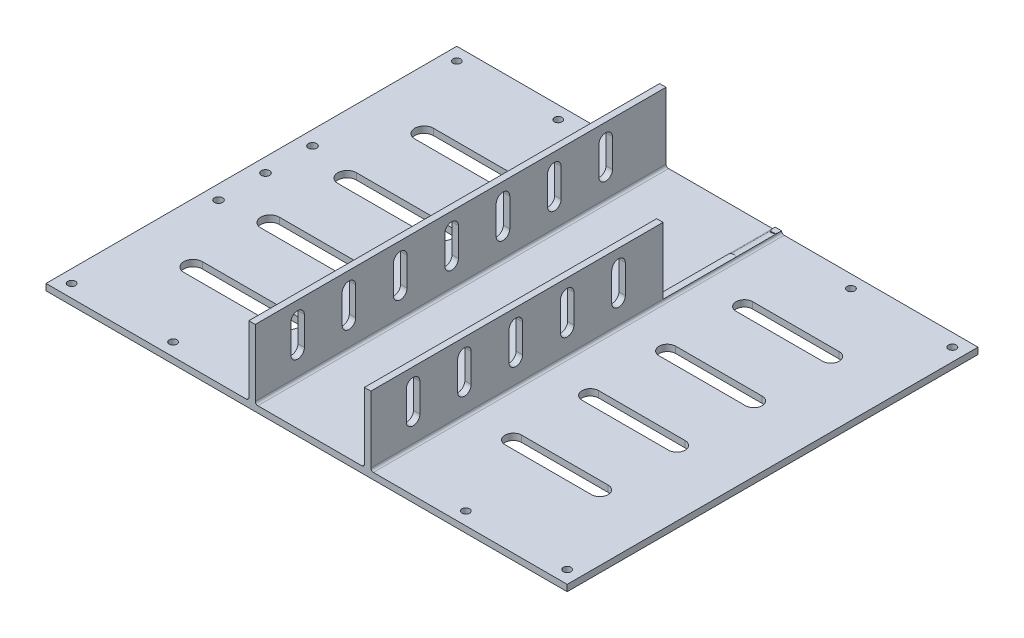
SolidWorks part; units mm, degrees
ref_plane "前视基准面" through (0, 0, 0) normal (0, 0, 1) x (1, 0, 0)
ref_plane "上视基准面" through (0, 0, 0) normal (0, 1, 0) x (1, 0, 0)
ref_plane "右视基准面" through (0, 0, 0) normal (1, 0, 0) x (0, 0, -1)
other "Configuration Table"
sketch "草图1" plane through (0, 0, 0) normal (0, 0, 1) x (1, 0, 0)
  line L0 (0, 0) -> (203, 0)
  line L1 (0, 0) -> (0, 2.5)
  line L2 (0, 2.5) -> (79, 2.5)
  line L3 (79, 2.5) -> (79, 32.5)
  line L4 (79, 32.5) -> (81.5, 32.5)
  line L5 (81.5, 32.5) -> (81.5, 2.5)
  line L6 (81.5, 2.5) -> (124, 2.5)
  line L7 (126.5, 2.5) -> (126.5, 32.5)
  line L8 (126.5, 32.5) -> (124, 32.5)
  line L9 (124, 32.5) -> (124, 2.5)
  line L11 (203, 2.5) -> (203, 0)
  line L12 (126.5, 2.5) -> (203, 2.5)
  dimension "D1" = 203
  dimension "D2" = 79
  dimension "D3" = 79
  dimension "D4" = 42.5
  dimension "D5" = 2.5
  dimension "D6" = 2.5
  dimension "D7" = 2.5
  dimension "D8" = 30
  dimension "D9" = 30
  dimension "D10" = 2.5
extrude "凸台-拉伸2" add sketch "草图1" along normal blind 160
fillet "圆角1" radius 1 1 edges at (81.5, 2.5, 80)
fillet "圆角2" radius 1 1 edges at (124, 2.5, 80)
fillet "圆角3" radius 1 2 edges at (79, 2.5, 80) (126.5, 2.5, 80)
sketch "草图2" plane through (0, 2.5, 0) normal (0, 1, 0) x (1, 0, 0)
  line L0 (78, 0) -> (0, 0) construction
  line L1 (0, -160) -> (0, 0) construction
  line L2 (78, -160) -> (0, -160) construction
  line L3 (203, -160) -> (203, 0) construction
  line L4 (203, 0) -> (127.5, 0) construction
  line L6 (203, -160) -> (127.5, -160) construction
  circle A0 centre (5, -5) radius 1.5
  circle A1 centre (5, -155) radius 1.5
  circle A2 centre (198, -5) radius 1.5
  circle A3 centre (198, -155) radius 1.5
  dimension "D9" = 3
  dimension "D10" = 3
  dimension "D11" = 3
  dimension "D12" = 3
  dimension "D1" = 5
  dimension "D2" = 5
  dimension "D3" = 5
  dimension "D4" = 5
  dimension "D5" = 5
  dimension "D6" = 5
  dimension "D7" = 5
  dimension "D8" = 5
extrude "切除-拉伸1" cut sketch "草图2" against normal blind 160
sketch "草图3" plane through (0, 2.5, 0) normal (0, 1, 0) x (1, 0, 0)
  line L0 (0, -160) -> (0, 0) construction
  line L1 (203, -160) -> (203, 0) construction
  line L4 (203, 0) -> (127.5, 0) construction
  line L5 (78, 0) -> (0, 0) construction
  line L6 (78, -160) -> (0, -160) construction
  circle A0 centre (44.5, -5) radius 1.5
  circle A1 centre (44.5, -155) radius 1.5
  circle A2 centre (158.5, -5) radius 1.5
  circle A3 centre (158.5, -155) radius 1.5
  dimension "D1" = 3
  dimension "D2" = 3
  dimension "D3" = 3
  dimension "D4" = 3
  dimension "D5" = 44.5
  dimension "D6" = 44.5
  dimension "D7" = 44.5
  dimension "D8" = 44.5
  dimension "D9" = 5
  dimension "D10" = 5
  dimension "D11" = 5
extrude "切除-拉伸2" cut sketch "草图3" against normal blind 160
sketch "草图4" plane through (0, 2.5, 0) normal (0, 1, 0) x (1, 0, 0)
  line L0 (23.0924, -35.8152) -> (60.3028, -35.8152) construction
  line L3 (23.0924, -32.1909) -> (60.3028, -32.1909)
  line L4 (23.0924, -39.4396) -> (60.3028, -39.4396)
  line L5 (23.0924, -69.4396) -> (60.3028, -69.4396)
  line L6 (23.0924, -62.1909) -> (60.3028, -62.1909)
  line L7 (23.0924, -65.8152) -> (60.3028, -65.8152) construction
  line L8 (23.0924, -99.4396) -> (60.3028, -99.4396)
  line L9 (23.0924, -92.1909) -> (60.3028, -92.1909)
  line L10 (23.0924, -95.8152) -> (60.3028, -95.8152) construction
  line L11 (23.0924, -129.4396) -> (60.3028, -129.4396)
  line L12 (23.0924, -122.1909) -> (60.3028, -122.1909)
  line L13 (23.0924, -125.8152) -> (60.3028, -125.8152) construction
  arc A2 (23.0924, -32.1909) -> (23.0924, -39.4396) centre (23.0924, -35.8152) ccw
  arc A3 (60.3028, -39.4396) -> (60.3028, -32.1909) centre (60.3028, -35.8152) ccw
  arc A4 (23.0924, -62.1909) -> (23.0924, -69.4396) centre (23.0924, -65.8152) ccw
  arc A5 (60.3028, -69.4396) -> (60.3028, -62.1909) centre (60.3028, -65.8152) ccw
  arc A6 (23.0924, -92.1909) -> (23.0924, -99.4396) centre (23.0924, -95.8152) ccw
  arc A7 (60.3028, -99.4396) -> (60.3028, -92.1909) centre (60.3028, -95.8152) ccw
  arc A8 (23.0924, -122.1909) -> (23.0924, -129.4396) centre (23.0924, -125.8152) ccw
  arc A9 (60.3028, -129.4396) -> (60.3028, -122.1909) centre (60.3028, -125.8152) ccw
  point P2 (41.6976, -35.8152)
  point P11 (41.6976, -65.8152)
  point P18 (41.6976, -95.8152)
  point P25 (41.6976, -125.8152)
  dimension "D1" = 4
extrude "切除-拉伸3" cut sketch "草图4" against normal blind 160
sketch "草图5" plane through (0, 2.5, 0) normal (0, 1, 0) x (1, 0, 0)
  line L0 (143.7888, -31.7728) -> (177.4701, -31.7728) construction
  line L1 (143.7888, -28.5294) -> (177.4701, -28.5294)
  line L2 (143.7888, -35.0162) -> (177.4701, -35.0162)
  line L3 (143.7888, -61.7728) -> (177.4701, -61.7728) construction
  line L4 (143.7888, -58.5294) -> (177.4701, -58.5294)
  line L5 (143.7888, -65.0162) -> (177.4701, -65.0162)
  line L6 (143.7888, -91.7728) -> (177.4701, -91.7728) construction
  line L7 (143.7888, -88.5294) -> (177.4701, -88.5294)
  line L8 (143.7888, -95.0162) -> (177.4701, -95.0162)
  line L9 (143.7888, -121.7728) -> (177.4701, -121.7728) construction
  line L10 (143.7888, -118.5294) -> (177.4701, -118.5294)
  line L11 (143.7888, -125.0162) -> (177.4701, -125.0162)
  arc A0 (143.7888, -28.5294) -> (143.7888, -35.0162) centre (143.7888, -31.7728) ccw
  arc A1 (177.4701, -35.0162) -> (177.4701, -28.5294) centre (177.4701, -31.7728) ccw
  arc A2 (143.7888, -58.5294) -> (143.7888, -65.0162) centre (143.7888, -61.7728) ccw
  arc A3 (177.4701, -65.0162) -> (177.4701, -58.5294) centre (177.4701, -61.7728) ccw
  arc A4 (143.7888, -88.5294) -> (143.7888, -95.0162) centre (143.7888, -91.7728) ccw
  arc A5 (177.4701, -95.0162) -> (177.4701, -88.5294) centre (177.4701, -91.7728) ccw
  arc A6 (143.7888, -118.5294) -> (143.7888, -125.0162) centre (143.7888, -121.7728) ccw
  arc A7 (177.4701, -125.0162) -> (177.4701, -118.5294) centre (177.4701, -121.7728) ccw
  point P2 (160.6294, -31.7728)
  point P11 (160.6294, -61.7728)
  point P18 (160.6294, -91.7728)
  point P25 (160.6294, -121.7728)
  dimension "D1" = 4
extrude "切除-拉伸4" cut sketch "草图5" against normal blind 160
sketch "草图6" plane through (126.5, 0, 0) normal (1, 0, 0) x (0, 0, -1)
  line L0 (-23.5108, 23.1947) -> (-23.5108, 12.1144) construction
  line L1 (-20.8726, 23.1947) -> (-20.8726, 12.1144)
  line L2 (-26.1489, 23.1947) -> (-26.1489, 12.1144)
  line L3 (-43.5108, 23.1947) -> (-43.5108, 12.1144) construction
  line L4 (-40.8726, 23.1947) -> (-40.8726, 12.1144)
  line L5 (-46.1489, 23.1947) -> (-46.1489, 12.1144)
  line L6 (-63.5108, 23.1947) -> (-63.5108, 12.1144) construction
  line L7 (-60.8726, 23.1947) -> (-60.8726, 12.1144)
  line L8 (-66.1489, 23.1947) -> (-66.1489, 12.1144)
  line L9 (-83.5108, 23.1947) -> (-83.5108, 12.1144) construction
  line L10 (-80.8726, 23.1947) -> (-80.8726, 12.1144)
  line L11 (-86.1489, 23.1947) -> (-86.1489, 12.1144)
  line L12 (-103.5108, 23.1947) -> (-103.5108, 12.1144) construction
  line L13 (-100.8726, 23.1947) -> (-100.8726, 12.1144)
  line L14 (-106.1489, 23.1947) -> (-106.1489, 12.1144)
  line L15 (-123.5108, 23.1947) -> (-123.5108, 12.1144) construction
  line L16 (-120.8726, 23.1947) -> (-120.8726, 12.1144)
  line L17 (-126.1489, 23.1947) -> (-126.1489, 12.1144)
  line L18 (-143.5108, 23.1947) -> (-143.5108, 12.1144) construction
  line L19 (-140.8726, 23.1947) -> (-140.8726, 12.1144)
  line L20 (-146.1489, 23.1947) -> (-146.1489, 12.1144)
  arc A0 (-20.8726, 23.1947) -> (-26.1489, 23.1947) centre (-23.5108, 23.1947) ccw
  arc A1 (-26.1489, 12.1144) -> (-20.8726, 12.1144) centre (-23.5108, 12.1144) ccw
  arc A2 (-40.8726, 23.1947) -> (-46.1489, 23.1947) centre (-43.5108, 23.1947) ccw
  arc A3 (-46.1489, 12.1144) -> (-40.8726, 12.1144) centre (-43.5108, 12.1144) ccw
  arc A4 (-60.8726, 23.1947) -> (-66.1489, 23.1947) centre (-63.5108, 23.1947) ccw
  arc A5 (-66.1489, 12.1144) -> (-60.8726, 12.1144) centre (-63.5108, 12.1144) ccw
  arc A6 (-80.8726, 23.1947) -> (-86.1489, 23.1947) centre (-83.5108, 23.1947) ccw
  arc A7 (-86.1489, 12.1144) -> (-80.8726, 12.1144) centre (-83.5108, 12.1144) ccw
  arc A8 (-100.8726, 23.1947) -> (-106.1489, 23.1947) centre (-103.5108, 23.1947) ccw
  arc A9 (-106.1489, 12.1144) -> (-100.8726, 12.1144) centre (-103.5108, 12.1144) ccw
  arc A10 (-120.8726, 23.1947) -> (-126.1489, 23.1947) centre (-123.5108, 23.1947) ccw
  arc A11 (-126.1489, 12.1144) -> (-120.8726, 12.1144) centre (-123.5108, 12.1144) ccw
  arc A12 (-140.8726, 23.1947) -> (-146.1489, 23.1947) centre (-143.5108, 23.1947) ccw
  arc A13 (-146.1489, 12.1144) -> (-140.8726, 12.1144) centre (-143.5108, 12.1144) ccw
  point P2 (-23.5108, 17.6545)
  point P11 (-43.5108, 17.6545)
  point P18 (-63.5108, 17.6545)
  point P25 (-83.5108, 17.6545)
  point P32 (-103.5108, 17.6545)
  point P39 (-123.5108, 17.6545)
  point P46 (-143.5108, 17.6545)
  dimension "D1" = 7
extrude "切除-拉伸5" cut sketch "草图6" against normal blind 160
sketch "草图7" plane through (0, 0, 0) normal (0, -1, 0) x (1, 0, 0)
  line L0 (0, 80) -> (203, 80)
  line L1 (0, 160) -> (0, 0) construction
  line L2 (203, 160) -> (203, 0) construction
  line L3 (5.5, 98.3) -> (5.5, 61.7)
  circle A0 centre (5.5, 98.3) radius 1.6
  circle A1 centre (5.5, 61.7) radius 1.6
  circle A2 centre (5.5, 80) radius 1.6
  point P9 (5.5, 80)
  dimension "D3" = 3.2
  dimension "D4" = 3.2
  dimension "D1" = 36.6
  dimension "D2" = 5.5
extrude "切除-拉伸6" cut sketch "草图7" against normal blind 10 contours A0 | A1 | A2
sketch "草图8" plane through (79, 0, 0) normal (-1, 0, 0) x (0, 0, 1)
  line L0 (0, 32.5) -> (160, 32.5)
  line L1 (160, 32.5) -> (160, 29.4229)
  line L2 (160, 32.5) -> (160, 3.5) construction
  line L3 (160, 29.4229) -> (0, 29.4229)
  line L4 (0, 29.4229) -> (0, 32.5)
extrude "切除-拉伸7" cut sketch "草图8" against normal up to surface (47.5 mm away) contours L4 L0 L1 L3 up to face at (126.5, 17.6545, 23.5108)
sketch "草图11" plane through (126.5, 0, 0) normal (1, 0, 0) x (0, 0, -1)
  line L0 (-157.1556, 12.5) -> (-142.1556, 12.5)
  line L1 (-142.1556, 12.5) -> (-142.1556, 2.5)
  line L2 (-160, 2.5) -> (0, 2.5) construction
  line L3 (-142.1556, 2.5) -> (-157.1556, 2.5)
  line L4 (-157.1556, 2.5) -> (-157.1556, 12.5)
  dimension "D1" = 15
  dimension "D2" = 10
sketch "草图12" plane through (126.5, 0, 0) normal (1, 0, 0) x (0, 0, -1)
  line L0 (-17.2818, 13.5) -> (-2.2818, 13.5)
  line L1 (-2.2818, 13.5) -> (-2.2818, 3.5)
  line L2 (-160, 3.5) -> (0, 3.5) construction
  line L3 (-2.2818, 3.5) -> (-17.2818, 3.5)
  line L4 (-17.2818, 3.5) -> (-17.2818, 13.5)
  dimension "D1" = 15
  dimension "D2" = 10
extrude "切除-拉伸11" cut sketch "草图12" against normal up to surface (2.5 mm away) up to face at (124, 17.6545, 143.5108)
fillet "圆角7" radius 10 1 edges at (124, 3.5, 9.7818)
fillet "圆角8" radius 1 4 edges at (123.8461, 2.967, 17.2818) (126.5, 13.5, 9.7818) (124, 8.5, 17.2818) (126.5, 8.5, 17.2818)
fillet "圆角9" radius 1 3 edges at (123.8461, 2.967, 2.2818) (124, 8.5, 2.2818) (124, 13.5, 10.2818)
fillet "圆角10" radius 1 1 edges at (126.5, 9, 2.2818)
sketch "草图13" plane through (126.5, 0, 0) normal (1, 0, 0) x (0, 0, -1)
  line L0 (0, 29.4229) -> (-160, 29.4229) construction
  line L5 (0, 3.5) -> (-46.1489, 3.5)
  line L6 (0, 3.5) -> (0, 29.4229)
  line L7 (0, 29.4229) -> (-46.1489, 29.4229)
  line L8 (-46.1489, 3.5) -> (-46.1489, 29.4229)
  dimension "D1" = 46.1489
extrude "切除-拉伸12" cut sketch "草图13" against normal up to next
sketch "草图14" plane through (0, 0, 0) normal (0, -1, 0) x (1, 0, 0)
  line L5 (5.5, 109.3579) -> (5.5, 50.6421) construction
  line L6 (-5.7648, 80) -> (16.7648, 80) construction
  line L7 (-2.9939, 57.6247) -> (13.9939, 57.6247)
  line L8 (-2.9939, 57.6247) -> (-2.9939, 102.3753)
  line L9 (-2.9939, 102.3753) -> (13.9939, 102.3753)
  line L10 (13.9939, 57.6247) -> (13.9939, 102.3753)
  line L11 (5.5, 102.3753) -> (5.5, 57.6247) construction
  line L12 (-2.9939, 80) -> (13.9939, 80) construction
  point P0 (5.5, 80)
  point P1 (5.5, 80)
